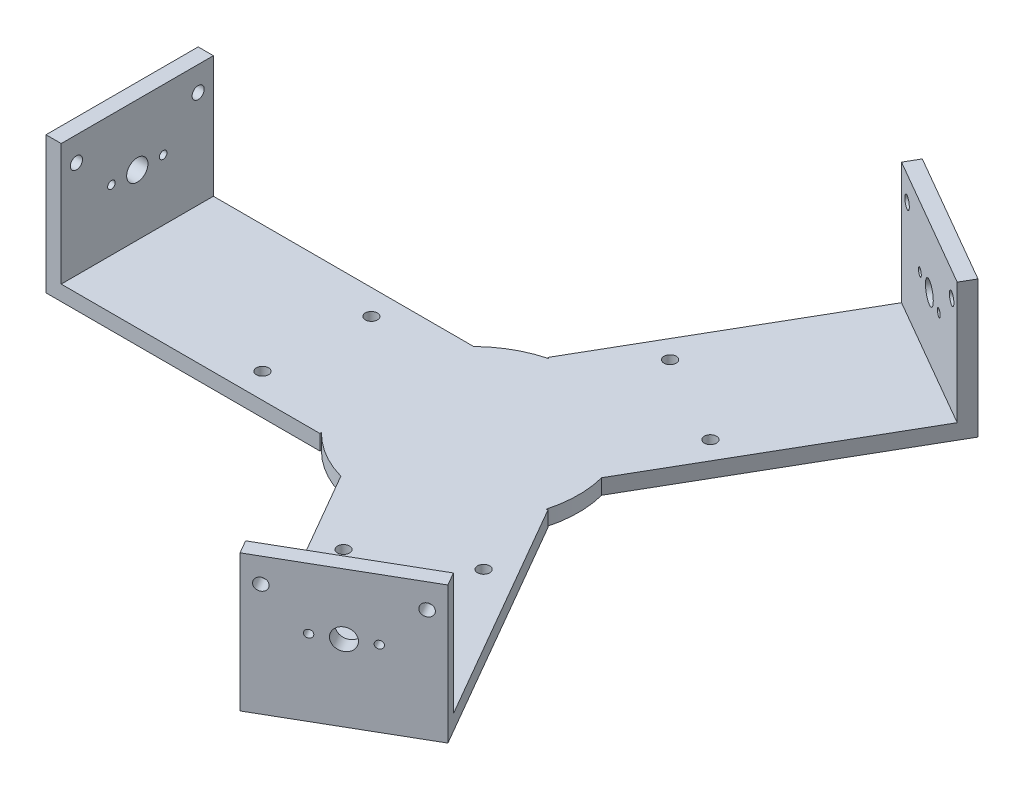
SolidWorks part; units mm, degrees
ref_plane "Plan de face" through (0, 0, 0) normal (0, 0, 1) x (1, 0, 0)
ref_plane "Plan de dessus" through (0, 0, 0) normal (0, 1, 0) x (1, 0, 0)
ref_plane "Plan de droite" through (0, 0, 0) normal (1, 0, 0) x (0, 0, -1)
sketch "Esquisse3" plane through (0, 0, 0) normal (0, 1, 0) x (1, 0, 0)
  line L0 (-150.1573, 0) -> (189.6273, 0) construction
  line L1 (-83.8395, -145.9242) -> (87.7229, 151.2306) construction
  line L2 (-78.0725, 135.2255) -> (117.7517, -203.9519) construction
  line L3 (-125, 131.2995) -> (-125, -153.5705) construction
  line L4 (-25, -25) -> (-115, -25)
  line L6 (-25, 25) -> (-24.4949, 25)
  line L7 (-115, -25) -> (-115, 25)
  line L8 (-25, -25) -> (-115, 25) construction
  line L9 (-25, 25) -> (-115, -25) construction
  line L10 (-24.4949, 25) -> (-115, 25)
  line L11 (33.8981, 8.7132) -> (79.1506, 87.0929)
  line L12 (35.8494, 112.0929) -> (79.1506, 87.0929)
  line L13 (-9.1506, 34.1506) -> (35.8494, 112.0929)
  line L14 (-9.4032, -33.7132) -> (35.8494, -112.0929)
  line L15 (79.1506, -87.0929) -> (35.8494, -112.0929)
  line L16 (34.1506, -9.1506) -> (79.1506, -87.0929)
  line L17 (-24.4949, 25) -> (-25, -25)
  line L18 (-9.1506, 34.1506) -> (33.8981, 8.7132)
  line L19 (-9.4032, -33.7132) -> (34.1506, -9.1506)
  circle A0 centre (0, 0) radius 125
  circle A1 centre (0, 0) radius 35
  circle A2 centre (0, 0) radius 125
  circle A3 centre (0, 0) radius 125
  point P9 (-70, 0)
  point P32 (0, 0)
  dimension "D1" = 250
  dimension "D4" = 70
  dimension "D2" = 120
  dimension "D3" = 120
  dimension "D5" = 10
  dimension "D6" = 50
  dimension "D7" = 90
  dimension "D8" = 3
extrude "Boss.-Extru.3" add sketch "Esquisse3" along normal blind 5 contours A1 L6 L10 L7 L4 L17 | A1 L14 L15 L16 L19 | L19 A1 L18 L17 | A1 L11 L12 L13 L18 | L18 A1 | A1 region at (-73.3157, 0, -0.0007) region at (0, 0, 0) region at (36.6572, 0, 63.4937) region at (14.7041, 0, -24.8843) region at (36.6585, 0, -63.4929)
sketch "Esquisse4" plane through (0, 5, 0) normal (0, 1, 0) x (1, 0, 0)
  line L0 (-25, -25) -> (-115, -25) construction
  line L1 (-115, 25) -> (-110, 25)
  line L2 (-115, 25) -> (-115, -25)
  line L3 (-115, -25) -> (-110, -25)
  line L4 (-110, 25) -> (-110, -25)
  line L5 (35.8494, 112.0929) -> (79.1506, 87.0929)
  line L6 (79.1506, 87.0929) -> (76.6506, 82.7628)
  line L7 (33.8981, 8.7132) -> (79.1506, 87.0929) construction
  line L8 (76.6506, 82.7628) -> (33.3494, 107.7628)
  line L9 (-9.1506, 34.1506) -> (35.8494, 112.0929) construction
  line L10 (33.3494, 107.7628) -> (35.8494, 112.0929)
  line L11 (79.1506, -87.0929) -> (76.6506, -82.7628)
  line L12 (34.1506, -9.1506) -> (79.1506, -87.0929) construction
  line L13 (76.6506, -82.7628) -> (33.3494, -107.7628)
  line L14 (-9.4032, -33.7132) -> (35.8494, -112.0929) construction
  line L15 (33.3494, -107.7628) -> (35.8494, -112.0929)
  line L16 (35.8494, -112.0929) -> (79.1506, -87.0929)
  dimension "D1" = 5
  dimension "D2" = 5
  dimension "D3" = 5
extrude "Boss.-Extru.4" add sketch "Esquisse4" along normal blind 40
sketch "Esquisse5" plane through (-110, 0, 0) normal (1, 0, 0) x (0, 0, -1)
  line L0 (-25, 25) -> (39.5019, 25) construction
  line L1 (-25, 45) -> (-25, 5) construction
  circle A0 centre (0, 25) radius 3.5
  circle A1 centre (-8.5, 25) radius 1.25
  circle A2 centre (8.5, 25) radius 1.25
  dimension "D1" = 7
  dimension "D4" = 2.5
  dimension "D5" = 2.5
  dimension "D2" = 8.5
  dimension "D3" = 8.5
extrude "Enlèv. mat.-Extru.1" cut sketch "Esquisse5" against normal through all
sketch "Esquisse6" plane through (55, 0, 95.2628) normal (-0.5, 0, -0.866) x (-0.866, 0, 0.5)
  line L0 (-25, 25) -> (25, 25) construction
  line L1 (-25, 45) -> (-25, 5) construction
  line L2 (25, 45) -> (25, 5) construction
  circle A0 centre (0, 25) radius 3.5
  circle A1 centre (-8.5, 25) radius 1.25
  circle A2 centre (8.5, 25) radius 1.25
  dimension "D1" = 7
  dimension "D4" = 2.5
  dimension "D5" = 2.5
  dimension "D2" = 8.5
  dimension "D3" = 8.5
extrude "Enlèv. mat.-Extru.2" cut sketch "Esquisse6" against normal through all
sketch "Esquisse7" plane through (55, 0, -95.2628) normal (-0.5, 0, 0.866) x (0.866, 0, 0.5)
  line L0 (-25, 25) -> (25, 25) construction
  line L1 (-25, 45) -> (-25, 5) construction
  line L2 (25, 45) -> (25, 5) construction
  circle A0 centre (0, 25) radius 3.5
  circle A1 centre (8.5, 25) radius 1.25
  circle A2 centre (-8.5, 25) radius 1.25
  dimension "D1" = 7
  dimension "D4" = 2.5
  dimension "D5" = 2.5
  dimension "D2" = 8.5
  dimension "D3" = 8.5
extrude "Enlèv. mat.-Extru.3" cut sketch "Esquisse7" against normal through all
sketch "Esquisse8" plane through (0, 5, 0) normal (0, 1, 0) x (1, 0, 0)
  circle A0 centre (11.9158, -54.1387) radius 2 construction
  circle A1 centre (40.5685, -36.7667) radius 2 construction
  circle A2 centre (11.5566, 53.5167) radius 2 construction
  circle A3 centre (40.9276, 37.3887) radius 2 construction
  circle A4 centre (-52.1251, -16.75) radius 2 construction
  circle A5 centre (-49.8434, 16.75) radius 2 construction
  circle A6 centre (11.9158, -54.1387) radius 2
  circle A7 centre (40.5685, -36.7667) radius 2
  circle A8 centre (11.5566, 53.5167) radius 2
  circle A9 centre (40.9276, 37.3887) radius 2
  circle A10 centre (-52.1251, -16.75) radius 2
  circle A11 centre (-49.8434, 16.75) radius 2
extrude "Enlèv. mat.-Extru.4" cut sketch "Esquisse8" against normal through all
sketch "Esquisse9" plane through (-115, 0, 0) normal (-1, 0, 0) x (0, 0, 1)
  circle A0 centre (-20, 37) radius 2 construction
  circle A1 centre (20, 37) radius 2 construction
  circle A2 centre (-20, 37) radius 2
  circle A3 centre (20, 37) radius 2
sketch "Esquisse10" plane through (57.5, 0, -99.5929) normal (0.5, 0, -0.866) x (-0.866, 0, -0.5)
  circle A0 centre (-20, 37) radius 2 construction
  circle A1 centre (20, 37) radius 2 construction
  circle A2 centre (-20, 37) radius 2
  circle A3 centre (20, 37) radius 2
sketch "Esquisse11" plane through (57.5, 0, 99.5929) normal (0.5, 0, 0.866) x (0.866, 0, -0.5)
  circle A0 centre (20, 37) radius 2 construction
  circle A1 centre (-20, 37) radius 2 construction
  circle A2 centre (20, 37) radius 2
  circle A3 centre (-20, 37) radius 2
extrude "Enlèv. mat.-Extru.5" cut sketch "Esquisse9" against normal through all
extrude "Enlèv. mat.-Extru.6" cut sketch "Esquisse10" against normal through all
extrude "Enlèv. mat.-Extru.7" cut sketch "Esquisse11" against normal up to next
